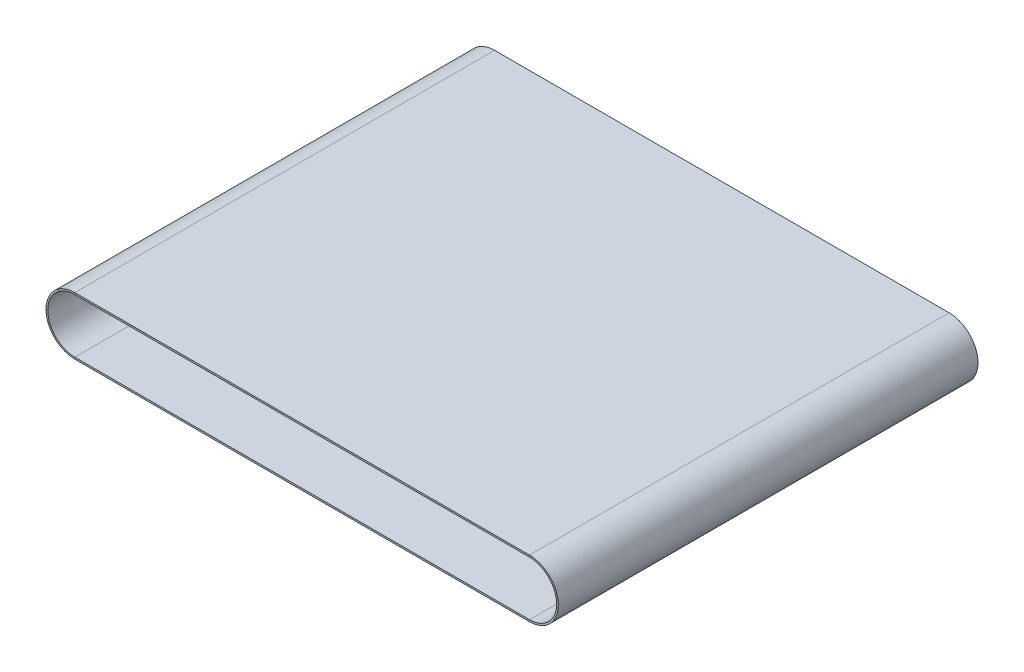
SolidWorks part; units mm, degrees
ref_plane "Front Plane" through (0, 0, 0) normal (0, 0, 1) x (1, 0, 0)
ref_plane "Top Plane" through (0, 0, 0) normal (0, 1, 0) x (1, 0, 0)
ref_plane "Right Plane" through (0, 0, 0) normal (1, 0, 0) x (0, 0, -1)
sketch "Sketch1" plane through (0, 0, 0) normal (0, 0, 1) x (1, 0, 0)
  line L0 (-260, -15.5) -> (0, -15.5)
  line L1 (0, 15.5) -> (-260, 15.5)
  arc A1 (-260, 15.5) -> (-260, -15.5) centre (-260, 0) ccw
  arc A3 (0, -15.5) -> (0, 15.5) centre (0, 0) ccw
  point P2 (0, 0)
  point P4 (0, 0)
  point P8 (0, 0)
  dimension "D1" = 31
  dimension "D2" = 260
sketch "Sketch2" plane through (0, 0, 0) normal (1, 0, 0) x (0, 0, -1)
  line L1 (-120, 15.5) -> (120, 15.5)
  line L2 (-120, 15.5) -> (-120, 16.5)
  line L3 (-120, 16.5) -> (120, 16.5)
  line L4 (120, 15.5) -> (120, 16.5)
  point P4 (0, 15.5)
  dimension "D1" = 1
  dimension "D2" = 240
sweep "Sweep1" add profiles "Sketch2" path "Sketch1"
